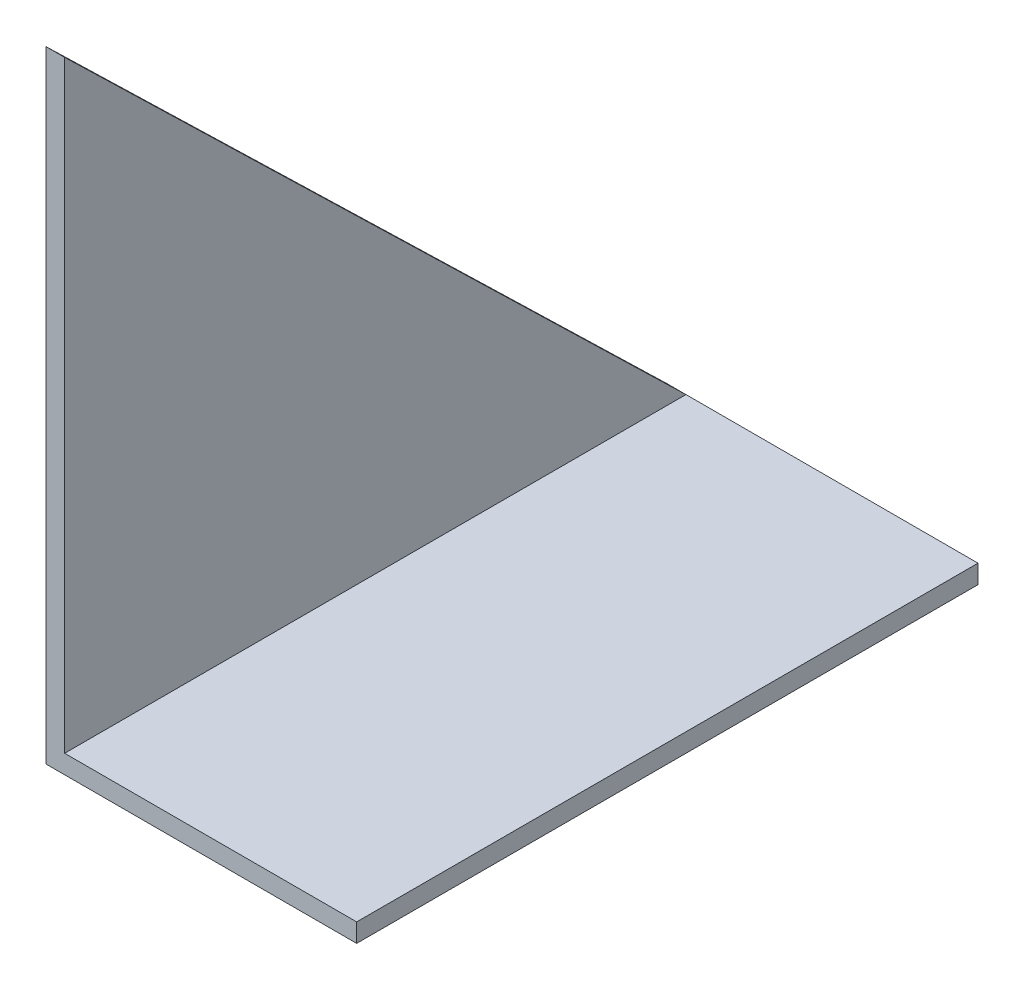
SolidWorks part; units mm, degrees
material "Acero al carbono no aleado"
ref_plane "Alzado" through (0, 0, 0) normal (0, 0, 1) x (1, 0, 0)
ref_plane "Planta" through (0, 0, 0) normal (0, 1, 0) x (1, 0, 0)
ref_plane "Vista lateral" through (0, 0, 0) normal (1, 0, 0) x (0, 0, -1)
sketch "Croquis1" plane through (0, 0, 0) normal (0, 0, 1) x (1, 0, 0)
  line L1 (1.5, -50) -> (-1.5, -50)
  line L2 (1.5, -50) -> (1.5, 50)
  line L3 (1.5, 50) -> (-1.5, 50)
  line L4 (-1.5, -50) -> (-1.5, 50)
  line L5 (1.5, -50) -> (-1.5, 50) construction
  line L6 (1.5, 50) -> (-1.5, -50) construction
  line L7 (1.5, -50) -> (48.5, -50)
  line L8 (1.5, -50) -> (1.5, -47)
  line L9 (1.5, -47) -> (48.5, -47)
  line L10 (48.5, -50) -> (48.5, -47)
  point P0 (0, 0)
  point P9 (48.5, -48.5)
  dimension "D1" = 100
  dimension "D2" = 50
  dimension "D3" = 3
  dimension "D4" = 3
extrude "Saliente-Extruir1" add sketch "Croquis1" along normal mid plane 100 contours L4 L1 L2 L3 | L7 L10 L9 L8 region at (0, 0, 0)
sketch "Croquis2" plane through (1.5, 0, 0) normal (1, 0, 0) x (0, 0, -1)
  line L0 (-50, 50) -> (50, -47)
  line L4 (-50, 50) -> (-50, -47)
  line L5 (-50, -47) -> (50, -47)
  line L6 (50, -47) -> (50, 50)
  line L7 (50, 50) -> (-50, 50)
  line L8 (-50, 50) -> (-50, -47)
  line L9 (-50, -47) -> (50, -47)
  line L10 (50, -47) -> (50, 50)
  line L11 (50, 50) -> (-50, 50)
  line M7 (50, -47) -> (50, 50)
  line M8 (50, 50) -> (-50, 50)
  dimension "D1" = 0
extrude "Cortar-Extruir1" cut sketch "Croquis2" against normal blind 100 contours L0 M8 M7 region at (1.5, 17.6667, -16.6667)
